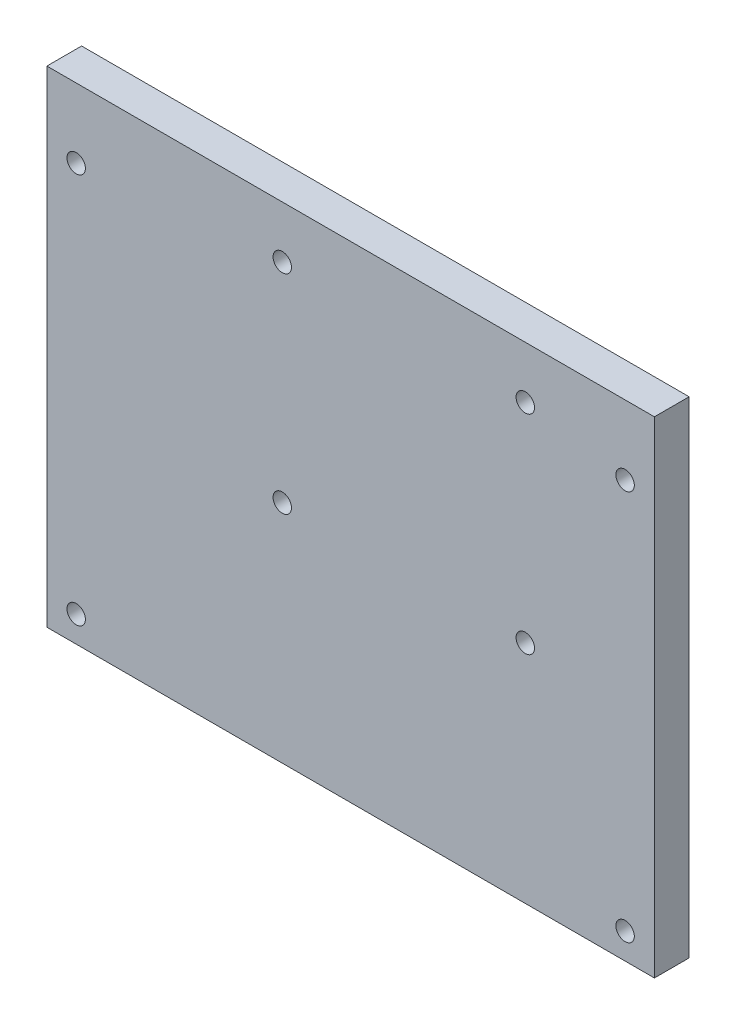
SolidWorks part; units mm, degrees
ref_plane "Front Plane" through (0, 0, 0) normal (0, 0, 1) x (1, 0, 0)
ref_plane "Top Plane" through (0, 0, 0) normal (0, 1, 0) x (1, 0, 0)
ref_plane "Right Plane" through (0, 0, 0) normal (1, 0, 0) x (0, 0, -1)
other "Configuration Table"
sketch "Sketch1" plane through (0, 0, 0) normal (0, 0, 1) x (1, 0, 0)
  line L1 (0, 0) -> (444.5, 0)
  line L2 (0, 0) -> (0, 355.6)
  line L3 (0, 355.6) -> (444.5, 355.6)
  line L4 (444.5, 0) -> (444.5, 355.6)
extrude "Boss-Extrude1" add sketch "Sketch1" along normal blind 25.4
sketch "Sketch2" plane through (0, 0, 0) normal (0, 0, 1) x (1, 0, 0)
  circle A0 centre (172.2374, 165.1) radius 6.7437
  circle A1 centre (350.0374, 165.1) radius 6.7437
  circle A2 centre (172.2374, 317.5) radius 6.7437
  circle A3 centre (350.0374, 317.5) radius 6.7437
extrude "Cut-Extrude1" cut sketch "Sketch2" along normal through all
sketch "Sketch3" plane through (0, 0, 0) normal (0, 0, 1) x (1, 0, 0)
  circle A0 centre (21.4376, 19.05) radius 6.7437
  circle A1 centre (423.0624, 19.05) radius 6.7437
  circle A2 centre (21.4376, 304.8) radius 6.7437
  circle A3 centre (423.0624, 304.8) radius 6.7437
extrude "Cut-Extrude2" cut sketch "Sketch3" along normal through all
sketch "Sketch4" plane through (0, 0, 0) normal (0, 0, 1) x (1, 0, 0)
  circle A0 centre (21.4376, 19.05) radius 11.1125
  circle A1 centre (423.0624, 19.05) radius 11.1125
  circle A2 centre (21.4376, 304.8) radius 11.1125
  circle A3 centre (423.0624, 304.8) radius 11.1125
extrude "Cut-Extrude3" cut sketch "Sketch4" along normal blind 9.525
